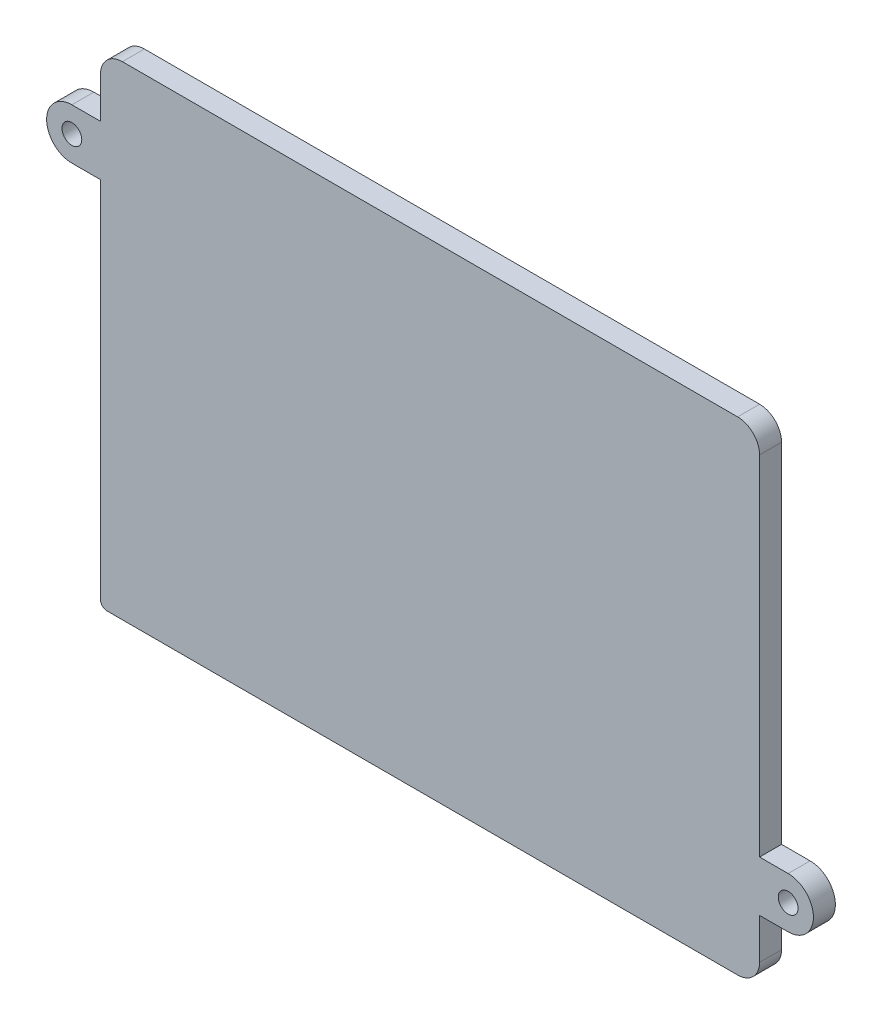
SolidWorks part; units mm, degrees
ref_plane "Front Plane" through (0, 0, 0) normal (0, 0, 1) x (1, 0, 0)
ref_plane "Top Plane" through (0, 0, 0) normal (0, 1, 0) x (1, 0, 0)
ref_plane "Right Plane" through (0, 0, 0) normal (1, 0, 0) x (0, 0, -1)
sketch "Sketch1" plane through (0, 0, 0) normal (0, 0, 1) x (1, 0, 0)
  line L43 (70, 11) -> (70, 7) construction
  line L44 (70, 7) -> (75, 7) construction
  line L46 (75, 7) -> (75, 11) construction
  line L48 (75, 11) -> (70, 11) construction
  line L49 (70, 26) -> (70, 11) construction
  line L52 (70, 11) -> (75, 11) construction
  line L53 (75, 11) -> (75, 26) construction
  line L56 (75, 26) -> (70, 26) construction
  line L75 (70, 30) -> (70, 26) construction
  line L76 (70, 26) -> (75, 26) construction
  line L77 (75, 26) -> (75, 30) construction
  line L78 (75, 30) -> (70, 30) construction
  line L79 (75, 7) -> (70, 7) construction
  line L80 (70, 7) -> (70, -45) construction
  line L81 (65, -50) -> (-65, -50) construction
  line L82 (-70, -45) -> (-70, 45) construction
  line L83 (-65, 50) -> (65, 50) construction
  line L84 (70, 45) -> (70, 30) construction
  line L85 (70, 30) -> (75, 30) construction
  line L86 (75, 30) -> (75, 50) construction
  line L87 (70, 55) -> (-70, 55) construction
  line L88 (-75, 50) -> (-75, 40.75) construction
  line L89 (-75, 40.75) -> (-81.5, 40.75) construction
  line L90 (-81.5, 29.25) -> (-75, 29.25) construction
  line L91 (-75, 29.25) -> (-75, -53.5) construction
  line L92 (-73.5, -55) -> (70, -55) construction
  line L93 (75, -50) -> (75, -40.75) construction
  line L94 (75, -40.75) -> (81.5, -40.75) construction
  line L95 (81.5, -29.25) -> (75, -29.25) construction
  line L96 (75, -29.25) -> (75, 7) construction
  line L97 (70, 11) -> (70, 7)
  line L98 (70, 7) -> (75, 7)
  line L99 (75, 7) -> (75, 11)
  line L100 (75, 11) -> (70, 11)
  line L101 (70, 26) -> (70, 11)
  line L102 (70, 11) -> (75, 11)
  line L104 (75, 11) -> (75, 26)
  line L105 (75, 26) -> (70, 26)
  line L106 (70, 30) -> (70, 26)
  line L107 (70, 26) -> (75, 26)
  line L110 (75, 26) -> (75, 30)
  line L112 (75, 30) -> (70, 30)
  line L113 (75, 7) -> (70, 7)
  line L114 (70, 7) -> (70, -45)
  line L115 (65, -50) -> (-65, -50)
  line L117 (-70, -45) -> (-70, 45)
  line L118 (-65, 50) -> (65, 50)
  line L138 (70, 45) -> (70, 30)
  line L139 (70, 30) -> (75, 30)
  line L140 (75, 30) -> (75, 50)
  line L141 (70, 55) -> (-70, 55)
  line L142 (-75, 50) -> (-75, 40.75)
  line L143 (-75, 40.75) -> (-81.5, 40.75)
  line L144 (-81.5, 29.25) -> (-75, 29.25)
  line L145 (-75, 29.25) -> (-75, -53.5)
  line L146 (-73.5, -55) -> (70, -55)
  line L147 (75, -50) -> (75, -40.75)
  line L148 (75, -40.75) -> (81.5, -40.75)
  line L149 (81.5, -29.25) -> (75, -29.25)
  line L150 (75, -29.25) -> (75, 7)
  circle A33 centre (81.5, -35) radius 2.25 construction
  arc A34 (65, -50) -> (70, -45) centre (65, -45) ccw construction
  arc A35 (-70, -45) -> (-65, -50) centre (-65, -45) ccw construction
  arc A36 (-65, 50) -> (-70, 45) centre (-65, 45) ccw construction
  arc A37 (70, 45) -> (65, 50) centre (65, 45) ccw construction
  arc A38 (75, 50) -> (70, 55) centre (70, 50) ccw construction
  arc A39 (-70, 55) -> (-75, 50) centre (-70, 50) ccw construction
  arc A40 (-81.5, 40.75) -> (-87.25, 35) centre (-81.5, 35) ccw construction
  arc A41 (-87.25, 35) -> (-81.5, 29.25) centre (-81.5, 35) ccw construction
  arc A42 (-75, -53.5) -> (-73.5, -55) centre (-73.5, -53.5) ccw construction
  arc A43 (70, -55) -> (75, -50) centre (70, -50) ccw construction
  arc A44 (81.5, -40.75) -> (87.25, -35) centre (81.5, -35) ccw construction
  arc A45 (87.25, -35) -> (81.5, -29.25) centre (81.5, -35) ccw construction
  circle A46 centre (81.5, -35) radius 2.25 construction
  circle A47 centre (-81.5, 35) radius 2.25 construction
  circle A48 centre (81.5, -35) radius 2.25
  arc A49 (65, -50) -> (70, -45) centre (65, -45) ccw
  arc A50 (-70, -45) -> (-65, -50) centre (-65, -45) ccw
  arc A51 (-65, 50) -> (-70, 45) centre (-65, 45) ccw
  arc A58 (70, 45) -> (65, 50) centre (65, 45) ccw
  arc A61 (75, 50) -> (70, 55) centre (70, 50) ccw
  arc A71 (-70, 55) -> (-75, 50) centre (-70, 50) ccw
  arc A72 (-81.5, 40.75) -> (-87.25, 35) centre (-81.5, 35) ccw
  arc A73 (-87.25, 35) -> (-81.5, 29.25) centre (-81.5, 35) ccw
  arc A74 (-75, -53.5) -> (-73.5, -55) centre (-73.5, -53.5) ccw
  arc A75 (70, -55) -> (75, -50) centre (70, -50) ccw
  arc A76 (81.5, -40.75) -> (87.25, -35) centre (81.5, -35) ccw
  arc A77 (87.25, -35) -> (81.5, -29.25) centre (81.5, -35) ccw
  circle A78 centre (81.5, -35) radius 2.25
  circle A79 centre (-81.5, 35) radius 2.25
extrude "Boss-Extrude1" add sketch "Sketch1" along normal blind 5 contours L97 | L97 | A76 A77 L149 L150 L98 L114 A49 L115 A50 L117 A51 L118 A58 L138 L112 L140 A61 L141 A71 L142 L143 A72 A73 L144 L145 A74 L146 A75 L147 L148 A79 A48 | L110 L112 L106 L105 | L104 L105 L101 L100 region at (72.5, 9, 0) region at (72.5, 18.5, 0) region at (0, 0, 0) region at (72.5, 4.9372, 0) region at (72.5, 28, 0)
sketch "Sketch3" plane through (0, 0, 0) normal (0, 0, 1) x (1, 0, 0)
  line L8 (-65, -50) -> (65, -50)
  line L9 (70, -45) -> (70, 45)
  line L10 (-65, 50) -> (65, 50)
  line L11 (-70, 45) -> (-70, -45)
  line L12 (-68.5, 45) -> (-68.5, -45)
  line L13 (-65, -48.5) -> (65, -48.5)
  line L14 (68.5, -45) -> (68.5, 45)
  line L15 (-65, 48.5) -> (65, 48.5)
  arc A0 (70, 45) -> (65, 50) centre (65, 45) ccw construction
  arc A1 (65, -50) -> (70, -45) centre (65, -45) ccw construction
  arc A3 (-70, -45) -> (-65, -50) centre (-65, -45) ccw construction
  arc A12 (-65, 50) -> (-70, 45) centre (-65, 45) ccw construction
  arc A13 (70, 45) -> (65, 50) centre (65, 45) ccw
  arc A16 (65, -50) -> (70, -45) centre (65, -45) ccw
  arc A19 (-70, -45) -> (-65, -50) centre (-65, -45) ccw
  arc A20 (-65, 50) -> (-70, 45) centre (-65, 45) ccw
  arc A21 (-68.5, -45) -> (-65, -48.5) centre (-65, -45) ccw
  arc A22 (65, -48.5) -> (68.5, -45) centre (65, -45) ccw
  arc A23 (68.5, 45) -> (65, 48.5) centre (65, 45) ccw
  arc A24 (-65, 48.5) -> (-68.5, 45) centre (-65, 45) ccw
  dimension "D1" = 1.5
extrude "Boss-Extrude2" add sketch "Sketch3" against normal blind 2 contours L12 A24 L15 A23 L14 A22 L13 A21 region at (0, 0, 0)
